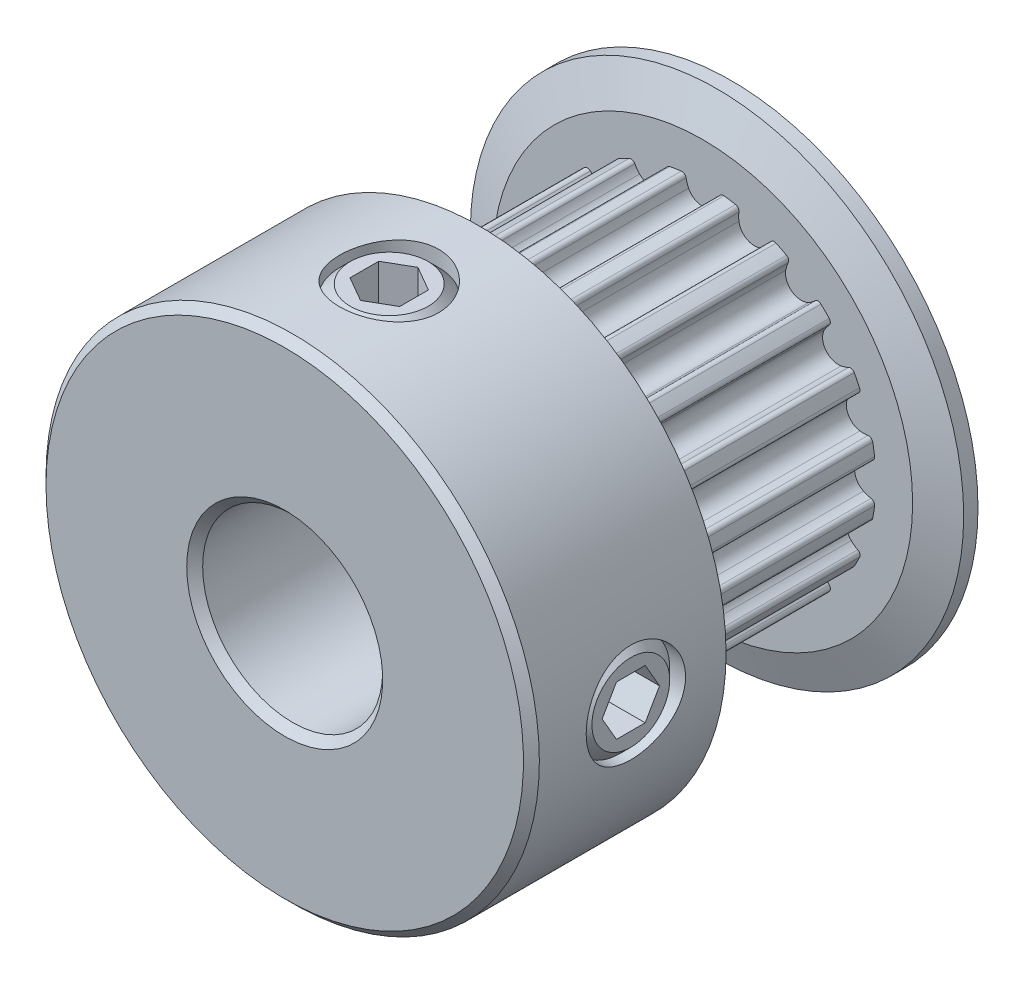
SolidWorks part; units mm, degrees
ref_plane "Front Plane" through (0, 0, 0) normal (0, 0, 1) x (1, 0, 0)
ref_plane "Top Plane" through (0, 0, 0) normal (0, 1, 0) x (1, 0, 0)
ref_plane "Right Plane" through (0, 0, 0) normal (1, 0, 0) x (0, 0, -1)
sketch "Sketch1" plane through (0, 0, 0) normal (0, 0, 1) x (1, 0, 0)
  line L1 (-1.7499, 5.3585) -> (1.7499, 5.3585) construction
  line L4 (0, 0) -> (0, 5.3585) construction
  line L5 (0, 5.3585) -> (0, 11.2095) construction
  line L6 (0, 6.3625) -> (1.9751, 6.0482) construction
  line L7 (1.9751, 6.0482) -> (2.6648, 5.8229) construction
  line L8 (1.9751, 6.0482) -> (1.7499, 5.3585) construction
  line L9 (-1.9751, 6.0482) -> (-1.7499, 5.3585) construction
  line L10 (-1.8963, 5.8067) -> (-2.841, 8.6995)
  line L11 (-2.841, 8.6995) -> (2.841, 8.6995)
  line L12 (2.841, 8.6995) -> (1.8963, 5.8067)
  circle A0 centre (0, 0) radius 6.3625 construction
  circle A1 centre (0, 0) radius 8.6995 construction
  circle A2 centre (0, 0) radius 6.1085 construction
  arc A3 (-0.4989, 5.6703) -> (0.4989, 5.6703) centre (0, 5.9135) ccw
  arc A4 (-0.4989, 5.6703) -> (-0.5855, 5.9387) centre (0.4, 6.1085) cw
  arc A5 (-1.8963, 5.8067) -> (-0.7518, 6.0621) centre (0, 0) cw
  arc A6 (-0.5855, 5.9387) -> (-0.7518, 6.0621) centre (-0.7333, 5.9132) ccw
  arc A7 (1.8963, 5.8067) -> (0.7518, 6.0621) centre (0, 0) ccw
  arc A8 (0.5855, 5.9387) -> (0.7518, 6.0621) centre (0.7333, 5.9132) cw
  arc A9 (0.4989, 5.6703) -> (0.5855, 5.9387) centre (-0.4, 6.1085) ccw
  point P6 (0, 20.9083)
  point P11 (0, 6.3625)
  point P13 (0, 8.6995)
  point P14 (0, 6.1085)
  dimension "D1" = 9.6989
  dimension "D2" = 4.847
sketch "Sketch2" plane through (0, 0, 0) normal (1, 0, 0) x (0, 0, -1)
  line L0 (-7.875, 3.175) -> (7.875, 3.175)
  line L1 (-7.875, 3.175) -> (-7.875, 8.6995)
  line L2 (-1.01, 8.6995) -> (-7.875, 8.6995)
  line L3 (-1.515, 3.175) -> (-1.515, 8.6995) construction
  line L4 (-1.515, 8.6995) -> (-0.505, 8.6995) construction
  line L5 (-0.505, 8.6995) -> (-0.505, 6.1085) construction
  line L6 (-0.505, 6.1085) -> (6.865, 6.1085)
  line L7 (6.865, 6.1085) -> (6.865, 8.6995) construction
  line L8 (6.865, 8.6995) -> (7.875, 8.6995) construction
  line L9 (7.875, 8.6995) -> (7.875, 3.175)
  line L10 (-7.875, 0) -> (7.875, 0) construction
  line L11 (7.37, 8.6995) -> (6.865, 7.404)
  line L12 (-0.505, 7.404) -> (-1.01, 8.6995)
  line L14 (-0.505, 7.404) -> (-0.505, 6.1085)
  line L15 (6.865, 6.1085) -> (6.865, 7.404)
  line L16 (7.37, 8.6995) -> (7.875, 8.6995)
  arc A0 (-0.505, 7.404) -> (-1.01, 8.6995) centre (-2.4192, 7.404) ccw construction
  arc A1 (6.865, 7.404) -> (7.37, 8.6995) centre (8.7792, 7.404) cw construction
  point P12 (-0.505, 7.404)
  point P14 (-1.01, 8.6995)
  point P20 (6.865, 7.404)
  point P21 (7.37, 8.6995)
  point P25 (6.865, 0)
  point P26 (-0.505, 0)
  dimension "OA" = 15.75
  dimension "Bore" = 6.35
  dimension "Outside Width" = 8.38
  dimension "Inside Width" = 7.37
revolve "Revolve1" add sketch "Sketch2" angle 360 mid plane about L10
sketch "Sketch3" plane through (0, 0, 0) normal (0, 0, 1) x (1, 0, 0)
  line L6 (2.841, 8.6995) -> (-2.841, 8.6995)
  line L7 (1.8963, 5.8067) -> (2.841, 8.6995)
  line L8 (-2.841, 8.6995) -> (-1.8963, 5.8067)
  line L9 (2.841, 8.6995) -> (-2.841, 8.6995)
  line L10 (1.8963, 5.8067) -> (2.841, 8.6995)
  line L11 (-2.841, 8.6995) -> (-1.8963, 5.8067)
  arc A8 (1.8963, 5.8067) -> (0.7518, 6.0621) centre (0, 0) ccw
  arc A9 (0.7518, 6.0621) -> (0.5855, 5.9387) centre (0.7333, 5.9132) ccw
  arc A10 (0.4989, 5.6703) -> (0.5855, 5.9387) centre (-0.4, 6.1085) ccw
  arc A11 (-0.4989, 5.6703) -> (0.4989, 5.6703) centre (0, 5.9135) ccw
  arc A12 (-0.5855, 5.9387) -> (-0.4989, 5.6703) centre (0.4, 6.1085) ccw
  arc A13 (-0.5855, 5.9387) -> (-0.7518, 6.0621) centre (-0.7333, 5.9132) ccw
  arc A14 (-0.7518, 6.0621) -> (-1.8963, 5.8067) centre (0, 0) ccw
  arc A15 (1.8963, 5.8067) -> (0.7518, 6.0621) centre (0, 0) ccw
  arc A16 (0.7518, 6.0621) -> (0.5855, 5.9387) centre (0.7333, 5.9132) ccw
  arc A17 (0.4989, 5.6703) -> (0.5855, 5.9387) centre (-0.4, 6.1085) ccw
  arc A18 (-0.4989, 5.6703) -> (0.4989, 5.6703) centre (0, 5.9135) ccw
  arc A19 (-0.5855, 5.9387) -> (-0.4989, 5.6703) centre (0.4, 6.1085) ccw
  arc A20 (-0.5855, 5.9387) -> (-0.7518, 6.0621) centre (-0.7333, 5.9132) ccw
  arc A21 (-0.7518, 6.0621) -> (-1.8963, 5.8067) centre (0, 0) ccw
  dimension "D1" = 0
extrude "Cut-Extrude1" cut sketch "Sketch3" against normal up to vertex (6.865 mm away) from vertex up to point (0, 6.1085, -6.865) starting at point (0, 6.1085, 0.505)
pattern_circular "CirPattern1" count 20 over 360 about axis through (0, 0, 7.875) along (0, 0, 1) of "Cut-Extrude1"
sketch "Sketch4" plane through (0, 0, 0) normal (1, 0, 0) x (0, -1, 0)
  line L0 (0, -0.505) -> (0, -7.875) construction
  line L1 (-3.175, -7.875) -> (3.175, -7.875) construction
  line L2 (7.404, -0.505) -> (-7.404, -0.505) construction
  circle A0 centre (0, -4.19) radius 1.7526
extrude "Cut-Extrude2" cut sketch "Sketch4" along normal through all
ref_plane "Plane1" through (0, 0, 4.19) normal (0, 0, 1) x (1, 0, 0)
sketch "Sketch5" plane through (0, 0, 4.19) normal (0, 0, 1) x (1, 0, 0)
  line L0 (0, 0) -> (0, 8.6995) construction
  line L1 (3.175, -1.3716) -> (3.175, 0)
  line L2 (3.556, -1.7526) -> (8.1401, -1.7526)
  line L3 (3.175, 0) -> (8.6995, 0) construction
  line L4 (3.175, 0) -> (8.5211, 0)
  line L5 (8.5211, 0) -> (8.5211, -1.3716)
  line L6 (3.556, -1.7526) -> (3.175, -1.3716)
  line L7 (8.5211, -1.3716) -> (8.1401, -1.7526)
  circle A0 centre (0, 0) radius 8.6995 construction
  circle A1 centre (0, 0) radius 3.175 construction
  point P2 (3.175, -1.7526)
  point P11 (8.5211, -1.7526)
revolve "Revolve2" add sketch "Sketch5" angle 360 mid plane about L4
sketch "Sketch6" plane through (8.5211, 5.3841, 0) normal (-1, 0, 0) x (0, -1, 0)
  line L1 (5.3841, 5.2019) -> (4.5078, 4.6959)
  line L2 (4.5078, 4.6959) -> (4.5078, 3.6841)
  line L3 (4.5078, 3.6841) -> (5.3841, 3.1781)
  line L4 (5.3841, 3.1781) -> (6.2604, 3.6841)
  line L5 (6.2604, 3.6841) -> (6.2604, 4.6959)
  line L6 (6.2604, 4.6959) -> (5.3841, 5.2019)
  circle A0 centre (5.3841, 4.19) radius 0.8763 construction
  dimension "D1" = 1.7526
extrude "Cut-Extrude3" cut sketch "Sketch6" along normal blind 1.3144
pattern_circular "CirPattern3" count 2 over 90 about axis through (0, 0, 7.875) along (0, 0, 1) of "Cut-Extrude2", "Revolve2", "Cut-Extrude3"
chamfer "Chamfer1" distance 0.2807 angle 45 2 edges at (3.175, 0, 7.875) (8.6995, 0, 7.875)
ref_axis "Center Axis 1" through (0, 0, -7.875) along (0, 0, 1)
ref_plane "Contact Plane 1" through (0, 0, 7.875) normal (0, 0, 1) x (1, 0, 0)
ref_plane "Contact Plane 2" through (0, 0, -7.875) normal (0, 0, -1) x (-1, 0, 0)
equation "\"D2@Sketch1\"= \"D1@Sketch1\" / 2"
equation "\"D1@Sketch6\" = \"Set Screw@Sketch4\" / 2"
equation "\"D1@Cut-Extrude3\" = \"D1@Sketch6\"*.75"
